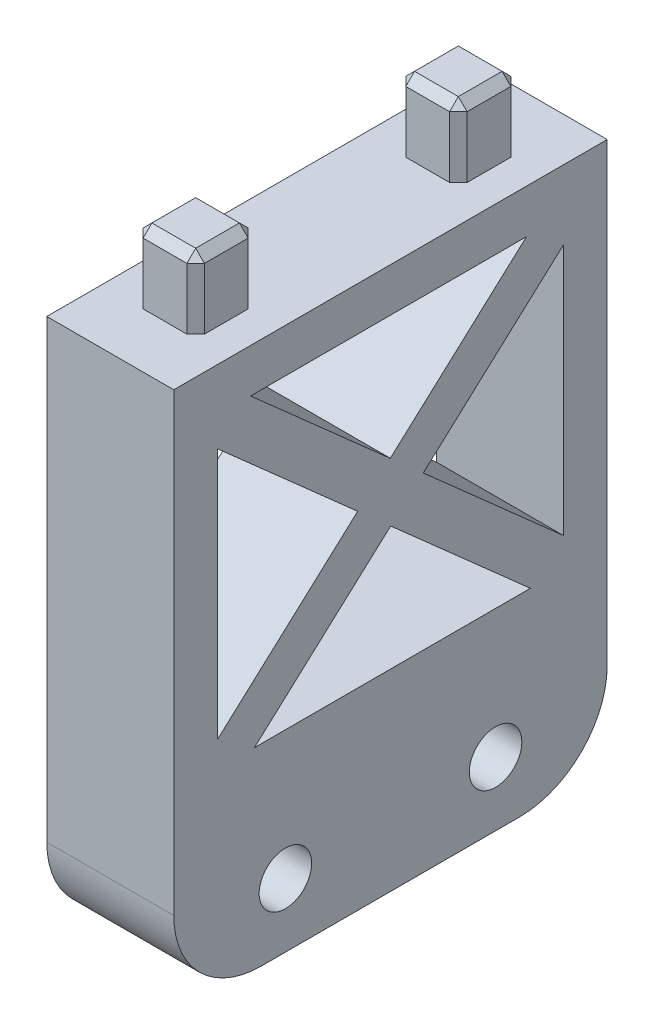
SolidWorks part; units mm, degrees
ref_plane "Front Plane" through (0, 0, 0) normal (0, 0, 1) x (1, 0, 0)
ref_plane "Top Plane" through (0, 0, 0) normal (0, 1, 0) x (1, 0, 0)
ref_plane "Right Plane" through (0, 0, 0) normal (1, 0, 0) x (0, 0, -1)
sketch "Sketch1" plane through (0, 0, 0) normal (0, 1, 0) x (1, 0, 0)
  line L1 (-7.25, -24.75) -> (7.25, -24.75)
  line L2 (-7.25, -24.75) -> (-7.25, 24.75)
  line L3 (-7.25, 24.75) -> (7.25, 24.75)
  line L4 (7.25, -24.75) -> (7.25, 24.75)
  line L5 (-7.25, -24.75) -> (7.25, 24.75) construction
  line L6 (-7.25, 24.75) -> (7.25, -24.75) construction
  point P0 (0, 0)
  dimension "D1" = 49.5
  dimension "D2" = 14.5
extrude "Boss-Extrude1" add sketch "Sketch1" along normal blind 70
fillet "Fillet1" radius 10 2 edges at (0, 0, -24.75) (0, 0, 24.75)
sketch "Sketch2" plane through (7.25, 0, 0) normal (1, 0, 0) x (0, 0, -1)
  line L0 (0, 0) -> (-12, 0) construction
  line L1 (-14.75, 0) -> (14.75, 0) construction
  line L2 (-12, 0) -> (-12, 4.3) construction
  line L3 (-12, 4.3) -> (-12, 7.3) construction
  line L4 (0, 0) -> (0, 10.6339) construction
  line L5 (12, 4.3) -> (12, 7.3) construction
  line L6 (12, 0) -> (12, 4.3) construction
  circle A0 centre (-12, 7.3) radius 3
  circle A1 centre (12, 7.3) radius 3
  dimension "D1" = 12
  dimension "D2" = 4.3
  dimension "D3" = 3
extrude "Cut-Extrude1" cut sketch "Sketch2" against normal through all
sketch "Sketch3" plane through (0, 70, 0) normal (0, 1, 0) x (1, 0, 0)
  line L0 (77.25, 8.5) -> (77.25, -8.5)
  line L1 (7.25, 0) -> (77.25, 0) construction
  line L2 (7.25, -24.75) -> (7.25, 24.75) construction
  line L3 (7.25, 24.75) -> (7.25, -24.75)
  line L4 (7.25, -24.75) -> (77.25, -8.5)
  line L5 (7.25, 24.75) -> (77.25, 8.5)
  point P7 (77.25, 0)
  dimension "D1" = 17
  dimension "D2" = 70
extrude "Boss-Extrude2" add sketch "Sketch3" against normal blind 8
sketch "Sketch5" plane through (77.25, 0, 0) normal (1, 0, 0) x (0, 0, -1)
  line L0 (-8.5, 66) -> (0, 66) construction
  line L1 (-8.5, 62) -> (-8.5, 70) construction
  line L2 (0, 66) -> (8.5, 66) construction
  line L3 (8.5, 62) -> (8.5, 70) construction
  circle A0 centre (-4.25, 66) radius 1.7
  circle A1 centre (4.25, 66) radius 1.7
  dimension "D2" = 3.4
  dimension "D3" = 3.4
  dimension "D1" = 8.5
extrude "Cut-Extrude2" cut sketch "Sketch5" against normal blind 15
ref_plane "Plane1" through (62.25, 0, 0) normal (1, 0, 0) x (0, 0, -1)
sketch "Sketch7" plane through (62.25, 0, 0) normal (1, 0, 0) x (0, 0, -1)
  line L0 (-7.5, 66) -> (-7.5, 70)
  line L1 (-1, 66) -> (-2.625, 68.8146) construction
  line L2 (-2.625, 68.8146) -> (-5.875, 68.8146) construction
  line L3 (-5.875, 68.8146) -> (-7.5, 66) construction
  line L4 (-7.5, 66) -> (-5.875, 63.1854)
  line L5 (-5.875, 63.1854) -> (-2.625, 63.1854)
  line L6 (-2.625, 63.1854) -> (-1, 66)
  line L7 (7.5, 66) -> (5.875, 68.8146) construction
  line L8 (5.875, 68.8146) -> (2.625, 68.8146) construction
  line L9 (2.625, 68.8146) -> (1, 66) construction
  line L10 (1, 66) -> (2.625, 63.1854)
  line L11 (2.625, 63.1854) -> (5.875, 63.1854)
  line L12 (5.875, 63.1854) -> (7.5, 66)
  line L13 (-8.5, 70) -> (8.5, 70) construction
  line L14 (-7.5, 70) -> (-1, 70)
  line L15 (-1, 70) -> (-1, 66)
  line L16 (1, 66) -> (1, 70)
  line L17 (1, 70) -> (7.5, 70)
  line L18 (7.5, 70) -> (7.5, 66)
  circle A0 centre (-4.25, 66) radius 2.8146 construction
  circle A1 centre (4.25, 66) radius 2.8146 construction
  dimension "D1" = 6.5
  dimension "D2" = 6.5
extrude "Cut-Extrude3" cut sketch "Sketch7" along normal blind 5
sketch "Sketch8" plane through (7.25, 0, 0) normal (1, 0, 0) x (0, 0, -1)
  line L0 (-24.75, 62) -> (-24.75, 17) construction
  line L1 (-24.75, 62) -> (-24.75, 10) construction
  line L2 (-24.75, 17) -> (24.75, 17) construction
  line L3 (24.75, 62) -> (24.75, 10) construction
  line L4 (0.0214, 36.1408) -> (15.9803, 22)
  line L5 (-8.5, 62) -> (8.5, 62) construction
  line L7 (-19.75, 24.9241) -> (-19.75, 53.6598)
  line L8 (-15.9803, 57) -> (15.5335, 57)
  line L9 (19.75, 25.3402) -> (19.75, 54.0759)
  line L10 (-0.0214, 42.8592) -> (15.5335, 57)
  line L11 (3.7428, 39.5239) -> (19.75, 25.3402)
  line L12 (-19.75, 53.6598) -> (-3.7428, 39.4761)
  line L13 (-19.75, 24.9241) -> (-3.7428, 39.4761)
  line L14 (-15.9803, 57) -> (-0.0214, 42.8592)
  line L15 (-15.5335, 22) -> (15.9803, 22)
  line L16 (-15.5335, 22) -> (0.0214, 36.1408)
  line L17 (3.7428, 39.5239) -> (19.75, 54.0759)
  point P5 (0, 39.5)
  dimension "D1" = 45
  dimension "D2" = 5
  dimension "D3" = 5
extrude "Cut-Extrude4" cut sketch "Sketch8" against normal through all
sketch "Sketch9" plane through (0, 70, 0) normal (0, 1, 0) x (1, 0, 0)
  line L0 (57.25, 13.1429) -> (57.25, -13.1429) construction
  line L1 (62.25, 7.5) -> (62.25, 1) construction
  line L2 (7.25, 24.75) -> (7.25, -24.75) construction
  line L3 (49.616, 9.7821) -> (17.551, 17.2257)
  line L4 (12.25, 16.0257) -> (12.25, -16.0257)
  line L5 (17.551, -17.2257) -> (49.616, -9.7821)
  line L6 (-7.25, -24.75) -> (7.25, -24.75)
  line L7 (7.25, -24.75) -> (77.25, -8.5)
  line L8 (77.25, -8.5) -> (77.25, 8.5)
  line L9 (77.25, 8.5) -> (7.25, 24.75)
  line L10 (7.25, 24.75) -> (-7.25, 24.75)
  line L11 (-7.25, 24.75) -> (-7.25, -24.75)
  line L13 (7.25, -24.75) -> (57.25, -13.1429) construction
  line L15 (57.25, 13.1429) -> (7.25, 24.75) construction
  line L18 (57.25, 10.1933) -> (57.25, -10.1933)
  line L21 (12.25, 16.0257) -> (35.453, 0)
  line L22 (49.616, 9.7821) -> (38.9722, 2.4307)
  line L23 (17.551, 17.2257) -> (38.9722, 2.4307)
  line L24 (57.25, 10.1933) -> (42.4915, 0)
  line L27 (42.4915, 0) -> (57.25, -10.1933)
  line L28 (38.9722, -2.4307) -> (49.616, -9.7821)
  line L29 (35.453, 0) -> (12.25, -16.0257)
  line L30 (38.9722, -2.4307) -> (17.551, -17.2257)
  dimension "D2" = 5
  dimension "D4" = 69.264
  dimension "D1" = 0
extrude "Cut-Extrude5" cut sketch "Sketch9" against normal blind 10 contours L29 L21 L4 | L3 L23 L22 | L24 L27 L18 | L28 L30 L5 region at (35.3797, 70, -9.8128) region at (19.9843, 70, 0) region at (35.3797, 70, 9.8128) region at (52.3305, 70, 0)
fillet "Fillet2" radius 1.5 2 edges at (57.25, 66, 10.1933) (57.25, 66, -10.1933)
fillet "Fillet3" radius 3 1 edges at (7.25, 62, 0)
sketch "Sketch11" plane through (62.25, 0, 0) normal (1, 0, 0) x (0, 0, -1)
  circle A0 centre (4.25, 66) radius 1.7 construction
  circle A1 centre (-4.25, 66) radius 1.7 construction
  circle A2 centre (4.25, 66) radius 1.7
  circle A3 centre (-4.25, 66) radius 1.7
extrude "Cut-Extrude7" cut sketch "Sketch11" against normal blind 3
sketch "Sketch12" plane through (0, 0, -24.75) normal (0, 0, -1) x (-1, 0, 0)
  line L4 (-7.25, 70) -> (-77.25, 70)
  line L5 (-77.25, 70) -> (-77.25, 62)
  line L6 (-77.25, 62) -> (-10.25, 62)
  line L7 (-7.25, 59) -> (-7.25, 70)
  line L8 (-7.25, 70) -> (-77.25, 70)
  line L9 (-77.25, 70) -> (-77.25, 62)
  line L10 (-77.25, 62) -> (-10.25, 62)
  line L11 (-7.25, 59) -> (-7.25, 70)
  arc A1 (-7.25, 59) -> (-10.25, 62) centre (-10.25, 59) ccw
  arc A2 (-7.25, 59) -> (-10.25, 62) centre (-10.25, 59) ccw
  dimension "D1" = 0
extrude "Cut-Extrude8" cut sketch "Sketch12" against normal through all
sketch "Sketch13" plane through (0, 70, 0) normal (0, 1, 0) x (1, 0, 0)
  line L0 (0, 15) -> (0, -15) construction
  line L1 (-3.5, -18.5) -> (3.5, -11.5) construction
  line L2 (-7.25, 0) -> (7.25, 0) construction
  line L3 (-7.25, 24.75) -> (-7.25, -24.75) construction
  line L4 (7.25, -24.75) -> (7.25, 24.75) construction
  line L5 (-3.5, 11.5) -> (3.5, 11.5)
  line L6 (-3.5, 11.5) -> (-3.5, 18.5)
  line L7 (-3.5, 18.5) -> (3.5, 18.5)
  line L8 (3.5, 11.5) -> (3.5, 18.5)
  line L9 (-3.5, 11.5) -> (3.5, 18.5) construction
  line L10 (-3.5, 18.5) -> (3.5, 11.5) construction
  line L11 (-3.5, -11.5) -> (3.5, -18.5) construction
  line L12 (3.5, -11.5) -> (3.5, -18.5)
  line L13 (-3.5, -18.5) -> (3.5, -18.5)
  line L14 (-3.5, -11.5) -> (-3.5, -18.5)
  line L15 (-3.5, -11.5) -> (3.5, -11.5)
  line L20 (-7.25, -24.75) -> (7.25, -24.75)
  line L21 (7.25, -24.75) -> (7.25, 24.75)
  line L22 (7.25, 24.75) -> (-7.25, 24.75)
  line L23 (-7.25, 24.75) -> (-7.25, -24.75)
  line L24 (-7.25, -24.75) -> (7.25, -24.75)
  line L25 (7.25, -24.75) -> (7.25, 24.75)
  line L26 (7.25, 24.75) -> (-7.25, 24.75)
  line L27 (-7.25, 24.75) -> (-7.25, -24.75)
  point P18 (0, 0)
  dimension "D1" = 7
  dimension "D2" = 15
  dimension "D3" = 7
  dimension "D4" = 0
extrude "Cut-Extrude9" cut sketch "Sketch13" against normal blind 8
chamfer "Chamfer1" distance 1 angle 45 16 edges at (0, 70, -11.5) (-3.5, 66, -11.5) (-3.5, 70, -15) (-3.5, 66, -18.5) (0, 70, -18.5) (3.5, 66, -18.5) (3.5, 70, -15) (3.5, 66, -11.5) (0, 70, 11.5) (-3.5, 66, 11.5) (-3.5, 70, 15) (-3.5, 66, 18.5) (0, 70, 18.5) (3.5, 66, 18.5) (3.5, 70, 15) (3.5, 66, 11.5)
